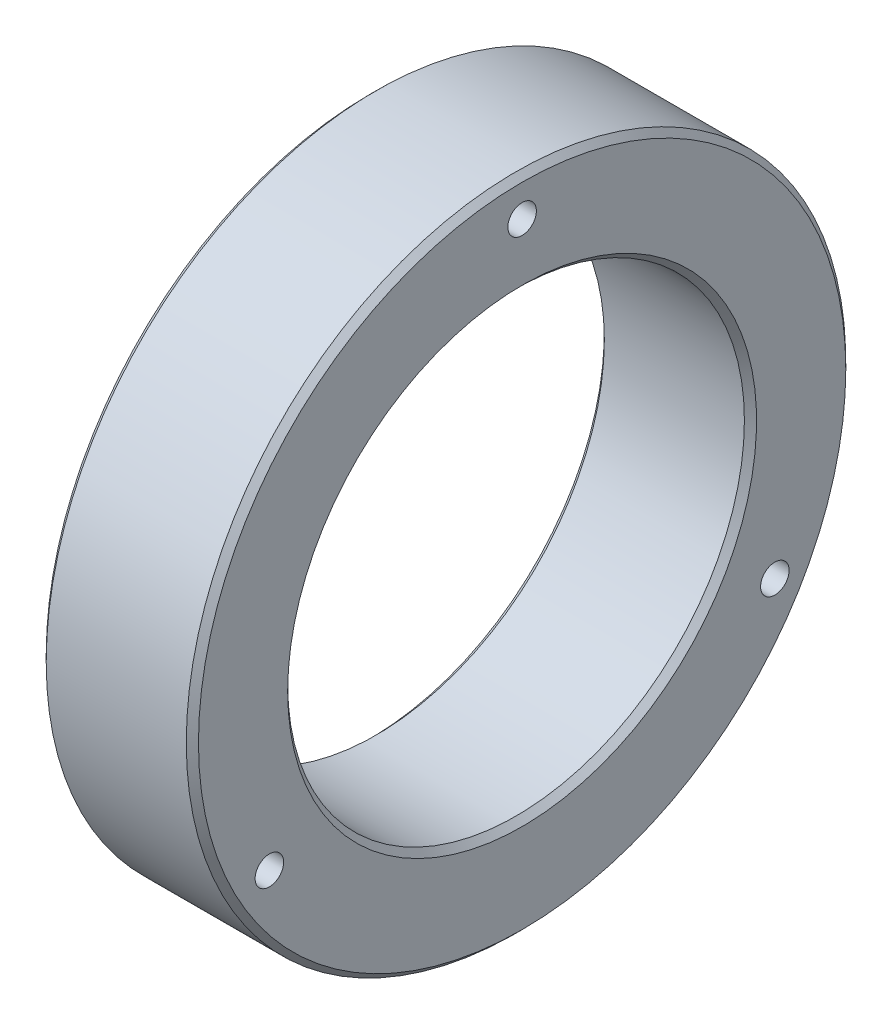
SolidWorks part; units mm, degrees
ref_plane "Front Plane" through (0, 0, 0) normal (0, 0, 1) x (1, 0, 0)
ref_plane "Top Plane" through (0, 0, 0) normal (0, 1, 0) x (1, 0, 0)
ref_plane "Right Plane" through (0, 0, 0) normal (1, 0, 0) x (0, 0, -1)
sketch "Sketch1" plane through (0, 0, 0) normal (0, 1, 0) x (1, 0, 0)
  line L0 (-19.05, 82.5246) -> (19.05, 82.5246)
  line L1 (19.05, 82.5246) -> (19.05, 57.15)
  line L2 (19.05, 57.15) -> (-19.05, 57.15)
  line L3 (-19.05, 57.15) -> (-19.05, 82.5246)
  line L4 (-44.45, 0) -> (44.45, 0) construction
  point P6 (0, 0)
  dimension "D1" = 38.1
  dimension "D2" = 25.3746
  dimension "D3" = 82.5246
  dimension "D4" = 19.05
revolve "Revolve1" add sketch "Sketch1" angle 360 about L4
chamfer "Chamfer1" distance 1.524 angle 45 4 edges at (19.05, 0, 57.15) (-19.05, 0, 57.15) (19.05, 0, 82.5246) (-19.05, 0, 82.5246)
sketch "Sketch2" plane through (0, 0, 0) normal (1, 0, 0) x (0, 0, -1)
  circle A0 centre (0, 73.025) radius 3.5687
  circle A1 centre (-63.246, -36.5252) radius 3.5687
  circle A2 centre (63.246, -36.5252) radius 3.5687
  point P6 (0, 0)
  dimension "D1" = 7.1374
  dimension "D2" = 7.1374
  dimension "D3" = 7.1374
  dimension "D4" = 63.246
  dimension "D5" = 126.492
  dimension "D6" = 109.5502
  dimension "D7" = 36.5252
extrude "Cut-Extrude2" cut sketch "Sketch2" along normal blind 76.2 from offset 19.05 offset against normal yes
sketch "Sketch3" plane through (0, 0, 0) normal (1, 0, 0) x (0, 0, -1)
  circle A0 centre (0, 73.025) radius 5.5626
  circle A1 centre (-63.246, -36.5252) radius 5.5626
  circle A2 centre (63.246, -36.5252) radius 5.5626
  point P6 (0, 0)
  dimension "D1" = 11.1252
  dimension "D2" = 11.1252
  dimension "D3" = 11.1252
  dimension "D4" = 63.246
  dimension "D5" = 126.492
  dimension "D6" = 109.5502
  dimension "D7" = 36.5252
extrude "Cut-Extrude4" cut sketch "Sketch3" along normal blind 9.652 from offset 19.05 offset against normal yes
sketch "Sketch4" plane through (0, 0, 0) normal (1, 0, 0) x (0, 0, -1)
  circle A0 centre (-69.85, 0) radius 3.9687
  circle A1 centre (69.85, 0) radius 3.9687
  point P4 (0, 0)
  dimension "D1" = 7.9375
  dimension "D2" = 7.9375
  dimension "D3" = 139.7
  dimension "D4" = 69.85
extrude "Cut-Extrude6" cut sketch "Sketch4" along normal blind 25.4 from offset 19.05 offset against normal yes
